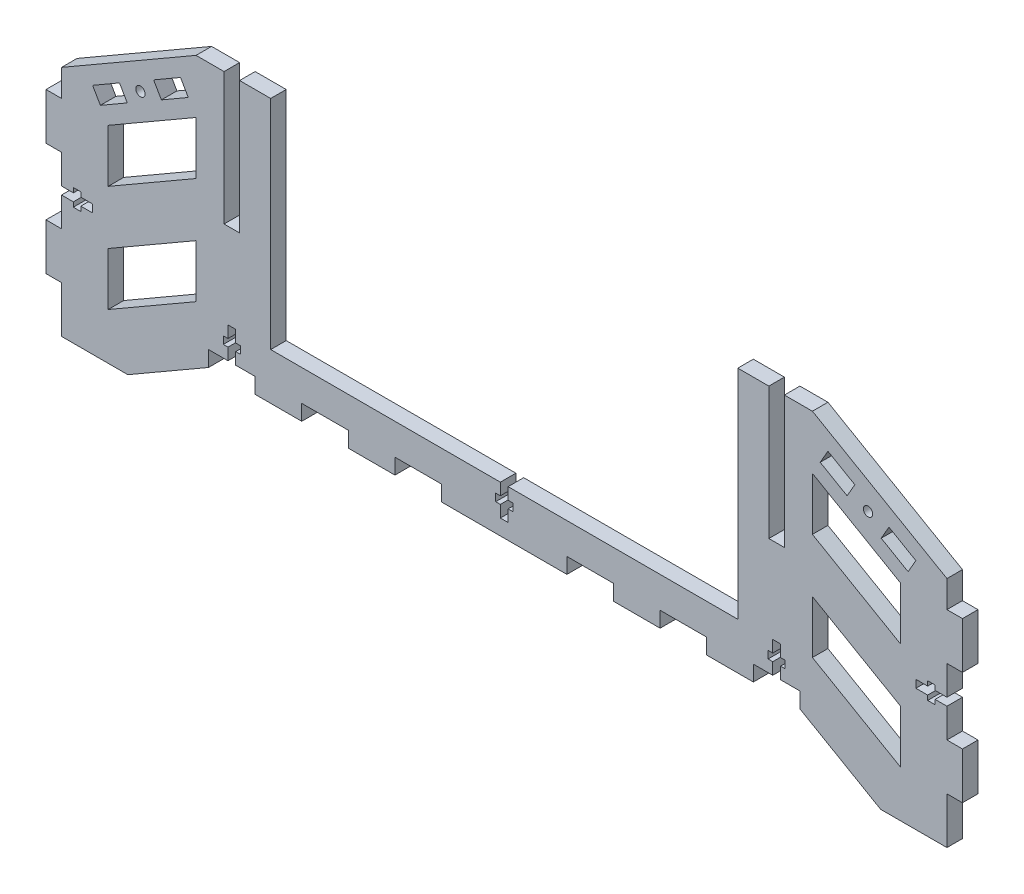
SolidWorks part; units mm, degrees
material "PMMA"
ref_plane "Front Plane" through (0, 0, 0) normal (0, 0, 1) x (1, 0, 0)
ref_plane "Top Plane" through (0, 0, 0) normal (0, 1, 0) x (1, 0, 0)
ref_plane "Right Plane" through (0, 0, 0) normal (1, 0, 0) x (0, 0, -1)
sketch "Schizzo1" plane through (0, 0, 0) normal (0, 0, 1) x (1, 0, 0)
  line L0 (-142.5, 75) -> (-142.5, 66.3397)
  line L1 (-142.5, 0) -> (142.5, 0)
  line L2 (142.5, 75) -> (142.5, 66.3397)
  line L3 (142.5, 75) -> (99.1987, 100)
  line L4 (99.1987, 100) -> (-99.1987, 100)
  line L5 (-99.1987, 100) -> (-142.5, 75)
  line L6 (95.1795, 85) -> (-95.1795, 85) construction
  line L7 (-95.1795, 85) -> (-127.5, 66.3397) construction
  line L8 (-127.5, 66.3397) -> (-127.5, 15) construction
  line L9 (-127.5, 15) -> (127.5, 15) construction
  line L10 (127.5, 15) -> (127.5, 66.3397) construction
  line L11 (127.5, 66.3397) -> (95.1795, 85) construction
  line L12 (-95.1795, 85) -> (-95.1795, 15) construction
  line L13 (95.1795, 85) -> (95.1795, 15) construction
  line L14 (-127.5, 66.3397) -> (127.5, 66.3397) construction
  line L15 (-142.5, 66.3397) -> (-147.5, 66.3397)
  line L16 (-147.5, 66.3397) -> (-147.5, 51.3397)
  line L17 (-147.5, 51.3397) -> (-142.5, 51.3397)
  line L18 (-142.5, 51.3397) -> (-142.5, 30)
  line L19 (-142.5, 30) -> (-147.5, 30)
  line L20 (-147.5, 30) -> (-147.5, 15)
  line L21 (-147.5, 15) -> (-142.5, 15)
  line L22 (-142.5, 15) -> (-142.5, 0)
  line L23 (-142.5, 75) -> (-142.5, 0) construction
  line L24 (142.5, 66.3397) -> (147.5, 66.3397)
  line L25 (142.5, 0) -> (142.5, 75) construction
  line L26 (147.5, 66.3397) -> (147.5, 51.3397)
  line L27 (147.5, 51.3397) -> (142.5, 51.3397)
  line L28 (142.5, 51.3397) -> (142.5, 30)
  line L29 (142.5, 30) -> (147.5, 30)
  line L30 (147.5, 30) -> (147.5, 15)
  line L31 (147.5, 15) -> (142.5, 15)
  line L32 (142.5, 15) -> (142.5, 0)
  point P2 (0, 0)
  dimension "D1" = 5
  dimension "D2" = 285
  dimension "D3" = 100
  dimension "D4" = 75
  dimension "D5" = 198.3975
  dimension "D7" = 190.359
  dimension "D8" = 15
  dimension "D9" = 150
  dimension "D10" = 21.3397
  dimension "D6" = 15
extrude "Estrusione-Estrusione1" add sketch "Schizzo1" along normal blind 5
sketch "Schizzo2" plane through (0, 0, 0) normal (0, 0, 1) x (1, 0, 0)
  line L0 (-99.1987, 82.6795) -> (-127.5, 66.3397)
  line L1 (-113.3494, 74.5096) -> (-120.8494, 87.5) construction
  line L2 (0, 0) -> (0, 100) construction
  line L3 (99.1987, 100) -> (-99.1987, 100) construction
  line L4 (-127.5, 49.3301) -> (-127.5, 66.3397)
  line L5 (99.1987, 31.3397) -> (99.1987, 48.3494)
  line L6 (-99.1987, 100) -> (-99.1987, 0) construction
  line L7 (99.1987, 31.3397) -> (127.5, 15)
  line L8 (127.5, 32.0096) -> (127.5, 15)
  line L9 (-95.1795, 15) -> (-121.1603, 0)
  line L10 (99.1987, 48.3494) -> (127.5, 32.0096)
  line L11 (-121.1603, 0) -> (121.1603, 0)
  line L12 (121.1603, 0) -> (95.1795, 15)
  line L13 (95.1795, 15) -> (-95.1795, 15)
  line L14 (-142.5, 0) -> (142.5, 0) construction
  line L15 (-99.1987, 31.3397) -> (-127.5, 15)
  line L16 (-99.1987, 65.6699) -> (-99.1987, 82.6795)
  line L17 (99.1987, 65.6699) -> (99.1987, 82.6795)
  line L18 (127.5, 49.3301) -> (99.1987, 65.6699)
  line L19 (127.5, 49.3301) -> (127.5, 66.3397)
  line L20 (-127.5, 49.3301) -> (-99.1987, 65.6699)
  line L21 (-99.1987, 48.3494) -> (-127.5, 32.0096)
  line L22 (-127.5, 32.0096) -> (-127.5, 15)
  line L23 (-99.1987, 31.3397) -> (-99.1987, 48.3494)
  line L24 (99.1987, 82.6795) -> (127.5, 66.3397)
  line L25 (-99.1987, 100) -> (-142.5, 75) construction
  line L26 (-127.5, 66.3397) -> (-135, 79.3301) construction
  line L27 (-132.5, 75) -> (-123.8397, 80)
  line L28 (-132.5, 75) -> (-130, 70.6699)
  line L29 (-130, 70.6699) -> (-121.3397, 75.6699)
  line L30 (-123.8397, 80) -> (-121.3397, 75.6699)
  line L31 (-104.1987, 91.3397) -> (-101.6987, 87.0096)
  line L32 (-104.1987, 91.3397) -> (-112.859, 86.3397)
  line L33 (-112.859, 86.3397) -> (-110.359, 82.0096)
  line L34 (-101.6987, 87.0096) -> (-110.359, 82.0096)
  line L35 (132.5, 75) -> (130, 70.6699)
  line L36 (130, 70.6699) -> (121.3397, 75.6699)
  line L37 (123.8397, 80) -> (121.3397, 75.6699)
  line L38 (132.5, 75) -> (123.8397, 80)
  line L39 (104.1987, 91.3397) -> (112.859, 86.3397)
  line L40 (104.1987, 91.3397) -> (101.6987, 87.0096)
  line L41 (101.6987, 87.0096) -> (110.359, 82.0096)
  line L42 (112.859, 86.3397) -> (110.359, 82.0096)
  circle A0 centre (-117.0994, 81.0048) radius 1.5
  circle A1 centre (117.0994, 81.0048) radius 1.5
  point P42 (-131.25, 72.8349)
  point P44 (-131.25, 72.8349)
  point P51 (-117.0994, 81.0048)
  dimension "D4" = 3
  dimension "D1" = 15
  dimension "D2" = 10
  dimension "D3" = 5
extrude "Taglio-Estrusione2" cut sketch "Schizzo2" along direction (0, 0, 1) on the side of the normal through all
sketch "Schizzo5" plane through (0, 0, 0) normal (0, 0, 1) x (1, 0, 0)
  line L0 (-95.1795, 15) -> (-95.1795, 20)
  line L1 (-95.1795, 20) -> (-80.1795, 20)
  line L2 (-80.1795, 20) -> (-80.1795, 15)
  line L3 (-80.1795, 15) -> (-95.1795, 15)
  line L4 (-65.1795, 20) -> (-65.1795, 15)
  line L5 (-65.1795, 15) -> (-50.1795, 15)
  line L6 (-50.1795, 15) -> (-50.1795, 20)
  line L7 (-50.1795, 20) -> (-65.1795, 20)
  line L8 (-35.1795, 15) -> (-35.1795, 20)
  line L9 (-35.1795, 20) -> (-20.1795, 20)
  line L10 (-20.1795, 20) -> (-20.1795, 15)
  line L11 (-20.1795, 15) -> (-35.1795, 15)
  line L12 (-127.5, 15) -> (127.5, 15) construction
  line L13 (-95.1795, 85) -> (-95.1795, 15) construction
  line L14 (0, 15) -> (0, 100) construction
  line L15 (35.1795, 15) -> (35.1795, 20)
  line L16 (20.1795, 15) -> (35.1795, 15)
  line L17 (20.1795, 20) -> (20.1795, 15)
  line L18 (35.1795, 20) -> (20.1795, 20)
  line L19 (50.1795, 15) -> (50.1795, 20)
  line L20 (65.1795, 15) -> (50.1795, 15)
  line L21 (65.1795, 20) -> (65.1795, 15)
  line L22 (50.1795, 20) -> (65.1795, 20)
  line L23 (95.1795, 15) -> (95.1795, 20)
  line L24 (80.1795, 15) -> (95.1795, 15)
  line L25 (80.1795, 20) -> (80.1795, 15)
  line L26 (95.1795, 20) -> (80.1795, 20)
  line L27 (-95.1795, 57.5) -> (95.1795, 57.5) construction
  line L28 (-95.1795, 15) -> (-121.1603, 0) construction
  line L29 (95.1795, 85) -> (95.1795, 15) construction
  line L30 (99.1987, 100) -> (-99.1987, 100) construction
  line L31 (90.1795, 100) -> (85.1795, 100)
  line L32 (-90.1795, 100) -> (-85.1795, 100)
  line L33 (-90.1795, 100) -> (-90.1795, 57.5)
  line L34 (-90.1795, 57.5) -> (-85.1795, 57.5)
  line L35 (-85.1795, 100) -> (-85.1795, 57.5)
  line L36 (90.1795, 100) -> (90.1795, 57.5)
  line L37 (90.1795, 57.5) -> (85.1795, 57.5)
  line L38 (85.1795, 100) -> (85.1795, 57.5)
  line L40 (-75.1795, 100) -> (75.1795, 100)
  line L41 (-75.1795, 100) -> (-75.1795, 30)
  line L42 (-75.1795, 30) -> (75.1795, 30)
  line L43 (75.1795, 100) -> (75.1795, 30)
  dimension "D1" = 5
  dimension "D2" = 15
  dimension "D3" = 15
  dimension "D4" = 15
  dimension "D5" = 42.5
  dimension "D6" = 42.5
  dimension "D7" = 5
  dimension "D8" = 5
  dimension "D9" = 10
  dimension "D10" = 10
  dimension "D11" = 15
  dimension "D12" = 190.359
  dimension "D13" = 40.359
extrude "Taglio-Estrusione3" cut sketch "Schizzo5" along direction (0, 0, 1) on the side of the normal through all
sketch "Schizzo6" plane through (0, 0, 0) normal (0, 0, 1) x (1, 0, 0)
  line L0 (-142.5, 51.3397) -> (-142.5, 30) construction
  line L1 (-142.5, 40.6699) -> (-120, 40.6699) construction
  line L2 (-142.5, 41.9199) -> (-138.7, 41.9199)
  line L3 (-138.7, 41.9199) -> (-138.7, 43.4199)
  line L4 (-138.7, 43.4199) -> (-136.3, 43.4199)
  line L5 (-136.3, 43.4199) -> (-136.3, 41.9199)
  line L6 (-136.3, 41.9199) -> (-132.5, 41.9199)
  line L7 (-132.5, 41.9199) -> (-132.5, 39.4199)
  line L8 (-132.5, 39.4199) -> (-136.3, 39.4199)
  line L9 (-136.3, 39.4199) -> (-136.3, 37.9199)
  line L10 (-136.3, 37.9199) -> (-138.7, 37.9199)
  line L11 (-138.7, 37.9199) -> (-138.7, 39.4199)
  line L12 (-138.7, 39.4199) -> (-142.5, 39.4199)
  line L13 (-142.5, 39.4199) -> (-142.5, 41.9199)
  line L14 (0, 0) -> (0, 100) construction
  line L15 (136.3, 43.4199) -> (136.3, 41.9199)
  line L16 (138.7, 43.4199) -> (136.3, 43.4199)
  line L17 (138.7, 41.9199) -> (138.7, 43.4199)
  line L18 (142.5, 41.9199) -> (138.7, 41.9199)
  line L19 (142.5, 39.4199) -> (142.5, 41.9199)
  line L20 (138.7, 39.4199) -> (142.5, 39.4199)
  line L21 (138.7, 37.9199) -> (138.7, 39.4199)
  line L22 (136.3, 37.9199) -> (138.7, 37.9199)
  line L23 (136.3, 39.4199) -> (136.3, 37.9199)
  line L24 (132.5, 39.4199) -> (136.3, 39.4199)
  line L25 (132.5, 41.9199) -> (132.5, 39.4199)
  line L26 (136.3, 41.9199) -> (132.5, 41.9199)
  line L27 (-90.1795, 57.5) -> (-85.1795, 57.5) construction
  line L28 (-87.6795, 57.5) -> (-87.6795, 2.5) construction
  line L29 (-80.1795, 20) -> (-95.1795, 20) construction
  line L30 (85.1795, 57.5) -> (90.1795, 57.5) construction
  line L31 (87.6795, 57.5) -> (87.6795, 20) construction
  line L32 (95.1795, 20) -> (80.1795, 20) construction
  line L33 (-87.6795, 20) -> (-87.6795, 30) construction
  line L34 (-88.9295, 20) -> (-88.9295, 23.8)
  line L35 (-88.9295, 23.8) -> (-90.4295, 23.8)
  line L36 (-90.4295, 23.8) -> (-90.4295, 26.2)
  line L37 (-90.4295, 26.2) -> (-88.9295, 26.2)
  line L38 (-88.9295, 26.2) -> (-88.9295, 30)
  line L39 (-88.9295, 30) -> (-86.4295, 30)
  line L40 (-86.4295, 30) -> (-86.4295, 26.2)
  line L41 (-86.4295, 26.2) -> (-84.9295, 26.2)
  line L42 (-84.9295, 26.2) -> (-84.9295, 23.8)
  line L43 (-84.9295, 23.8) -> (-86.4295, 23.8)
  line L44 (-86.4295, 23.8) -> (-86.4295, 20)
  line L45 (-86.4295, 20) -> (-88.9295, 20)
  line L46 (86.4295, 20) -> (88.9295, 20)
  line L47 (86.4295, 23.8) -> (86.4295, 20)
  line L48 (84.9295, 23.8) -> (86.4295, 23.8)
  line L49 (84.9295, 26.2) -> (84.9295, 23.8)
  line L50 (86.4295, 26.2) -> (84.9295, 26.2)
  line L51 (86.4295, 30) -> (86.4295, 26.2)
  line L52 (88.9295, 30) -> (86.4295, 30)
  line L53 (88.9295, 26.2) -> (88.9295, 30)
  line L54 (90.4295, 26.2) -> (88.9295, 26.2)
  line L55 (90.4295, 23.8) -> (90.4295, 26.2)
  line L56 (88.9295, 23.8) -> (90.4295, 23.8)
  line L57 (88.9295, 20) -> (88.9295, 23.8)
  line L58 (0, 32.4779) -> (0, 27.5221) construction
  line L59 (0, 20) -> (0, 30) construction
  line L60 (-1.25, 20) -> (-1.25, 23.8)
  line L61 (-1.25, 23.8) -> (-2.75, 23.8)
  line L62 (-2.75, 23.8) -> (-2.75, 26.2)
  line L63 (-2.75, 26.2) -> (-1.25, 26.2)
  line L64 (-1.25, 26.2) -> (-1.25, 30)
  line L65 (-1.25, 30) -> (1.25, 30)
  line L66 (1.25, 30) -> (1.25, 26.2)
  line L67 (1.25, 26.2) -> (2.75, 26.2)
  line L68 (2.75, 26.2) -> (2.75, 23.8)
  line L69 (2.75, 23.8) -> (1.25, 23.8)
  line L70 (1.25, 23.8) -> (1.25, 20)
  line L71 (1.25, 20) -> (-1.25, 20)
  line L73 (-75.1795, 30) -> (75.1795, 30) construction
  dimension "D1" = 5.5
  dimension "D2" = 2.5
  dimension "D3" = 1.25
  dimension "D4" = 2.75
  dimension "D5" = 2.4
  dimension "D6" = 10
  dimension "D7" = 5.5
  dimension "D8" = 2.5
  dimension "D9" = 1.25
  dimension "D10" = 2.75
  dimension "D11" = 2.4
  dimension "D12" = 10
  dimension "D13" = 90
  dimension "D14" = 90
  dimension "D15" = 5.5
  dimension "D16" = 2.5
  dimension "D17" = 1.25
  dimension "D18" = 2.75
  dimension "D19" = 2.4
  dimension "D20" = 10
  dimension "D21" = 90
  dimension "D22" = 90
extrude "Taglio-Estrusione4" cut sketch "Schizzo6" along direction (0, 0, 1) on the side of the normal through all
equation "\"Thickness\"=5"
equation "\"D1@Estrusione-Estrusione1\"=\"Thickness\""
equation "\"D1@Schizzo5\"=\"Thickness\""
equation "\"D7@Schizzo5\"=\"Thickness\""
equation "\"D9@Schizzo5\"=2*\"Thickness\""
equation "\"D10@Schizzo5\"=2*\"Thickness\""
equation "\"D1@Schizzo1\"=\"Thickness\""
equation "\"D3@Schizzo2\"=\"Thickness\""
